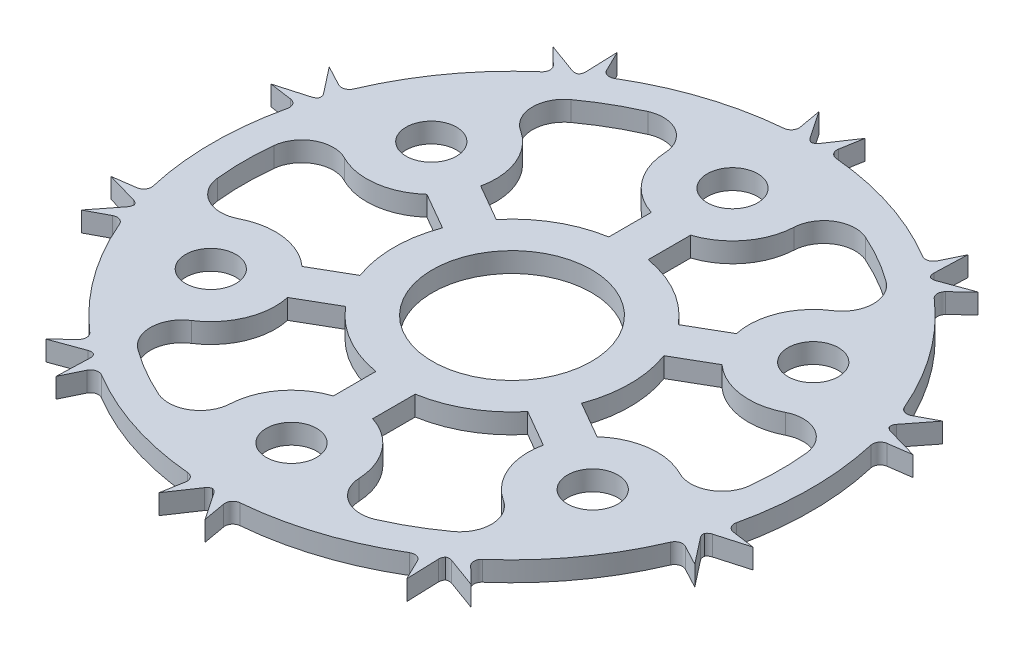
SolidWorks part; units mm, degrees
note: '?' marks a value the reader was unsure of.
material "Commercially Pure CP-Ti UNS R50700  Grade 4 (SS)"
ref_plane "Front Plane" through (0, 0, 0) normal (0, 0, 1) x (1, 0, 0)
ref_plane "Top Plane" through (0, 0, 0) normal (0, 1, 0) x (1, 0, 0)
ref_plane "Right Plane" through (0, 0, 0) normal (1, 0, 0) x (0, 0, -1)
other "Bounding Box"
ref_plane "Default Plane" through (13.8565, 3.175, 6.7999) normal (0, -1, 0) x (-1, 0, 0)
sketch "Sketch1" plane through (0, 0, 0) normal (0, 1, 0) x (1, 0, 0)
  line L0 (17.9605, -17.9605) -> (0, 0) construction
  line L1 (0, 0) -> (17.9605, 17.9605) construction
  line L2 (0, 0) -> (0, 25.4) construction
  circle A0 centre (0, 0) radius 25.4
  point P3 (0, 25.4)
  point P4 (25.4, 0)
  point P5 (-25.4, 0)
  point P6 (0, -25.4)
  point P7 (17.9605, 17.9605)
  point P8 (17.9605, -17.9605)
  dimension "D1" = 50.8
  dimension "D2" = 45
extrude "Boss-Extrude1" add sketch "Sketch1" along normal mid plane 15.24
ref_plane "Plane2" through (-25.4, 0, 0) normal (-1, 0, 0) x (0, 0, 1)
sketch "Sketch9" plane through (-25.4, 0, 0) normal (-1, 0, 0) x (0, 0, 1)
  line L0 (-0.635, -7.62) -> (0.635, -7.62)
  line L1 (-25.4, -7.62) -> (25.4, -7.62) construction
  line L2 (0.635, -7.62) -> (0.635, 0)
  line L3 (25.4, 7.62) -> (-25.4, 7.62) construction
  line L5 (-0.635, 0) -> (-0.635, -7.62)
  line L6 (0.635, -7.62) -> (0, -7.62) construction
  line L7 (0, -7.62) -> (0, 7.62) construction
  line L9 (-0.635, 0) -> (0.635, 0) construction
  line L10 (0.635, 0) -> (0.635, 7.62)
  line L11 (0.635, 7.62) -> (-0.635, 7.62)
  line L13 (-0.635, 7.62) -> (-0.635, 0)
  point P14 (0, 0)
  dimension "D2" = 1.27
extrude "Cut-Extrude4" cut sketch "Sketch9" against normal blind 0.635
sketch "Sketch4" plane through (0, 0, 0) normal (0, 0, 1) x (1, 0, 0)
  line L0 (-25.4, -7.62) -> (-22.225, -7.62)
  line L1 (-25.3921, -7.62) -> (25.4, -7.62) construction
  line L4 (25.4, 7.62) -> (-25.3921, 7.62) construction
  line L5 (-22.225, 7.62) -> (-25.4, 7.62)
  line L6 (-25.4, 7.62) -> (-25.4, -7.62)
  line L7 (-9.525, 0) -> (0, 0) construction
  line L8 (-22.225, -7.62) -> (-22.225, -5.08)
  line L9 (-22.225, -5.08) -> (-13.9469, -1.7687)
  line L10 (-13.9469, 1.7687) -> (-22.225, 5.08)
  line L11 (-22.225, 5.08) -> (-22.225, 7.62)
  arc A0 (-13.9469, 1.7687) -> (-13.9469, -1.7687) centre (-14.6544, 0) cw
  point P17 (-25.4, 0)
  dimension "D4" = 1.905
  dimension "D1" = 3.175
  dimension "D2" = 15.875
  dimension "D3" = 2.54
pattern_circular "CirPattern2" count 20 over 360 about axis through (0, 0, 0) along (0, 1, 0) of "Cut-Extrude4"
ref_axis "Axis1" through (0, -55, 0) along (0, 1, 0)
sketch "Sketch3" plane through (0, 7.62, 0) normal (0, 1, 0) x (1, 0, 0)
  line L0 (0, 0) -> (0, 17.78) construction
  line L1 (0, 17.78) -> (0, 25.4) construction
  circle A0 centre (0, 17.78) radius 1.397
  circle A1 centre (0, 0) radius 25.4 construction
  circle A2 centre (0, 17.78) radius 3.81
  dimension "D2" = 2.794
  dimension "D3" = 7.62
  dimension "D1" = 7.62
move or copy body "Body-Move/Copy1" [suppressed] parameters "D1"=0, "D2"=0, "D3"=0
revolve "Cut-Revolve2" cut sketch "Sketch4" angle 360 about axis through (0, -55, 0) along (0, 1, 0)
sketch "Sketch5" plane through (0, 7.62, 0) normal (0, 1, 0) x (1, 0, 0)
  circle A0 centre (0, 17.78) radius 3.81
  circle A1 centre (0, 17.78) radius 1.397 construction
  circle A3 centre (0, 17.78) radius 1.397
  circle A4 centre (0, 17.78) radius 3.81 construction
extrude "Boss-Extrude2" add sketch "Sketch5" against normal through all
sketch "Sketch12" plane through (0, 7.62, 0) normal (0, 1, 0) x (1, 0, 0)
  line L0 (-15.3979, 8.89) -> (0, 0) construction
  line L1 (-15.3979, -8.89) -> (-15.3979, 8.89) construction
  line L2 (-15.3979, 8.89) -> (0, 17.78) construction
  line L3 (-15.3979, -8.89) -> (0, 0) construction
  line L4 (0, 0) -> (0, 17.78) construction
  circle A0 centre (-15.3979, 8.89) radius 3.81
  circle A1 centre (0, 17.78) radius 3.81 construction
  dimension "D3" = 120
extrude "Boss-Extrude6" add sketch "Sketch12" against normal through all
sketch "Sketch17" plane through (0, 0, 0) normal (0, 1, 0) x (1, 0, 0)
  line L0 (0, 17.78) -> (0, 0) construction
  line L1 (0, 0) -> (-15.3979, 8.89) construction
  line L2 (0, 0) -> (-15.3979, -8.89) construction
  line L3 (-18.6975, -10.795) -> (-19.2474, -11.1125)
  line L4 (0, 21.59) -> (0, 22.225)
  line L5 (-17.3029, -5.5904) -> (-15.2513, -4.406)
  line L6 (-15.2513, 4.406) -> (-17.3029, 5.5904)
  line L7 (-13.4929, 12.1896) -> (-11.4413, 11.0051)
  line L8 (-3.81, 17.78) -> (-3.81, 15.411)
  circle A0 centre (0, 17.78) radius 3.81 construction
  circle A1 centre (-15.3979, 8.89) radius 3.81 construction
  arc A2 (0, 21.59) -> (-3.81, 17.78) centre (0, 17.78) ccw
  arc A3 (-13.4929, 12.1896) -> (-17.3029, 5.5904) centre (-15.3979, 8.89) ccw
  arc A5 (-3.81, 15.411) -> (-11.4413, 11.0051) centre (0, 0) ccw
  circle A6 centre (0, 17.78) radius 1.397 construction
  arc A7 (-17.3029, -5.5904) -> (-18.6975, -10.795) centre (-15.3979, -8.89) ccw
  circle A8 centre (0, 0) radius 22.225 construction
  circle A9 centre (0, 17.78) radius 1.397
  circle A10 centre (0, 0) radius 22.225 construction
  arc A11 (0, 22.225) -> (-19.2474, -11.1125) centre (0, 0) ccw
  arc A12 (-15.2513, 4.406) -> (-15.2513, -4.406) centre (0, 0) ccw
  circle A13 centre (-15.3979, 8.89) radius 1.397
  circle A15 centre (-15.3979, -8.89) radius 1.397
  dimension "D1" = 6.35
extrude "Cut-Extrude5" cut sketch "Sketch17" against normal through all both and the other way through all
pattern_circular "CirPattern1" count 3 over 360 about axis through (0, 0, 0) along (0, 1, 0) of "Boss-Extrude2", "Boss-Extrude6", "Cut-Extrude5"
sketch "Sketch24" plane through (0, -7.62, 0) normal (0, -1, 0) x (1, 0, 0)
  line L1 (5.4993, -9.525) -> (10.9985, 0)
  line L2 (10.9985, 0) -> (5.4993, 9.525)
  line L3 (5.4993, 9.525) -> (-5.4993, 9.525)
  line L4 (-5.4993, 9.525) -> (-10.9985, 0)
  line L5 (-10.9985, 0) -> (-5.4993, -9.525)
  line L6 (-5.4993, -9.525) -> (5.4993, -9.525)
  circle A0 centre (0, 0) radius 6.35 construction
  circle A1 centre (0, 0) radius 9.525 construction
  dimension "D1" = 12.7
  dimension "D2" = 19.05
extrude "Cut-Extrude7" cut sketch "Sketch24" against normal through all
sketch "Sketch33" [suppressed] plane through (0, -7.62, 0) normal (0, -1, 0) x (1, 0, 0)
  line L1 (-6.35, -6.35) -> (6.35, -6.35) construction
  line L2 (-6.35, -6.35) -> (-6.35, 6.35) construction
  line L3 (-6.35, 6.35) -> (6.35, 6.35) construction
  line L4 (6.35, -6.35) -> (6.35, 6.35) construction
  line L5 (-6.35, -6.35) -> (6.35, 6.35) construction
  line L6 (-6.35, 6.35) -> (6.35, -6.35) construction
  circle A0 centre (-6.35, 6.35) radius 2.4892
  circle A1 centre (6.35, 6.35) radius 2.4892
  circle A2 centre (6.35, -6.35) radius 2.4892
  circle A3 centre (-6.35, -6.35) radius 2.4892
  point P0 (0, 0)
  dimension "D1" = 4.9784
  dimension "D2" = 12.7
extrude "Cut-Extrude8" [suppressed] cut sketch "Sketch33" against normal through all
combine bodies "Combine3" [suppressed] bodies to combine 116 167
delete or keep bodies "Body-Delete/Keep 4" [suppressed] bodies 194
sketch "Sketch7" [suppressed] plane through (0, -8.255, 0) normal (0, -1, 0) x (1, 0, 0)
  circle A0 centre (0, 0) radius 44.45
  circle A1 centre (0, 0) radius 38.1 construction
  dimension "D1" = 6.35
extrude "Boss-Extrude4" [suppressed] add sketch "Sketch7" against normal offset from surface (19.685 mm away) 3.175 separate body
combine bodies "Combine2" [suppressed] operation type? add bodies to combine 110 114
sketch "Sketch15" [suppressed] plane through (0, 0, 0) normal (1, 0, 0) x (0, 0, -1)
  line L0 (-38.1, -8.255) -> (-43.18, -13.335)
  line L1 (-43.18, -13.335) -> (-36.83, -13.335)
  line L2 (-36.83, -13.335) -> (-31.75, -8.255)
  line L3 (-31.75, -8.255) -> (-38.1, -8.255)
  dimension "D1" = 5.08
  dimension "D2" = 45
  dimension "D3" = 6.35
ref_axis "Axis2" [suppressed] through (0, -9.0805, 0) along (0, 1, 0)?
revolve "Revolve1" [suppressed] add sketch "Sketch15" angle 360 about axis through (0, -9.0805, 0) along (0, 1, 0)
fillet "Fillet4" [suppressed] radius 6.35
sketch "Sketch27" [suppressed] plane through (0, 11.43, 0) normal (0, 1, 0) x (1, 0, 0)
  line L0 (37.5671, 6.35) -> (44.45, 6.35)
  line L1 (44.45, -6.35) -> (37.5671, -6.35)
  line L2 (38.1, 0) -> (44.45, 0) construction
  circle A0 centre (44.45, 0) radius 1.905
  arc A1 (37.5671, -6.35) -> (37.5671, 6.35) centre (0, 0) ccw
  circle A2 centre (0, 0) radius 38.1 construction
  arc A3 (44.45, 6.35) -> (44.45, -6.35) centre (44.45, 0) cw
  dimension "D2" = 3.81
  dimension "D3" = 6.35
  dimension "D1" = 6.35
extrude "Boss-Extrude13" [suppressed] add sketch "Sketch27" against normal blind 9.525
pattern_circular "CirPattern7" [suppressed] count 3 over 360
split "Split1" [suppressed] bodies to split 124
sketch "Sketch19" [suppressed] plane through (0, 11.43, 0) normal (0, 1, 0) x (1, 0, 0)
  line L0 (-20.447, 35.4152) -> (-19.177, 33.2155)
  line L1 (-20.447, -35.4152) -> (-19.177, -33.2155)
  line L2 (-40.894, 0) -> (0, 0) construction
  arc A0 (-19.177, 33.2155) -> (-19.177, -33.2155) centre (0, 0) ccw
  circle A1 centre (0, 0) radius 38.1 construction
  arc A2 (-20.447, 35.4152) -> (-20.447, -35.4152) centre (0, 0) ccw
  dimension "D2" = 2.54
  dimension "D3" = 0.254
  dimension "D1" = 120
extrude "Boss-Extrude10" [suppressed] add sketch "Sketch19" against normal blind 6.35 separate body
sketch "Sketch21" [suppressed] plane through (0, 11.43, 0) normal (0, 1, 0) x (1, 0, 0)
  line L0 (-19.177, 33.2155) -> (-19.05, 32.9956)
  line L1 (-19.177, -33.2155) -> (-19.05, -32.9956)
  line L2 (-19.177, 33.2155) -> (-20.447, 35.4152) construction
  line L3 (-20.447, -35.4152) -> (-19.177, -33.2155) construction
  arc A1 (-19.177, 33.2155) -> (-19.177, -33.2155) centre (0, 0) ccw construction
  arc A2 (-19.05, 32.9956) -> (-19.05, -32.9956) centre (0, 0) ccw
  arc A3 (-19.177, 33.2155) -> (-19.177, -33.2155) centre (0, 0) ccw
  circle A4 centre (0, 0) radius 38.1 construction
extrude "Boss-Extrude11" [suppressed] add sketch "Sketch21" against normal blind 3.1496
pattern_circular "CirPattern6" [suppressed] count 3 over 360
combine bodies "Combine4" [suppressed] bodies to combine 137 137 135 134
chamfer "Chamfer4" [suppressed] distance 0.635 angle 45
delete or keep bodies "Body-Delete/Keep 1" [suppressed] type delete bodies bodies 133
delete or keep bodies "Body-Delete/Keep 2" [suppressed] type delete bodies bodies 121
mirror "Mirror1" [suppressed] about plane through (0, 0, 0) normal (1, 0, 0)
delete or keep bodies "Body-Delete/Keep 3" [suppressed] type delete bodies bodies 121
sketch "Sketch28" [suppressed] plane through (0, 8.255, 0) normal (0, -1, 0) x (1, 0, 0)
  circle A0 centre (0, 0) radius 15.24
  dimension "D1" = 30.48
extrude "Boss-Extrude14" [suppressed] add sketch "Sketch28" along normal blind 0.635
sketch "Sketch29" [suppressed] plane through (0, 7.62, 0) normal (0, -1, 0) x (1, 0, 0)
  circle A0 centre (0, 0) radius 9.144
  dimension "D1" = 18.288
extrude "Boss-Extrude15" [suppressed] add sketch "Sketch29" along normal blind 10.16
sketch "Sketch30" plane through (0, -7.62, 0) normal (0, -1, 0) x (1, 0, 0)
  circle A12 centre (0, 0) radius 24.13
  circle A13 centre (0, 0) radius 21.59
  circle A14 centre (0, 0) radius 25.4 construction
  dimension "D1" = 1.27
  dimension "D2" = 2.54
extrude "Boss-Extrude16" add sketch "Sketch30" along normal blind 1.6002 separate body
sketch "Sketch31" plane through (0, -9.2202, 0) normal (0, -1, 0) x (1, 0, 0)
  line L0 (-5.207, 17.78) -> (-5.207, 23.5615)
  line L1 (-5.207, 23.5615) -> (5.207, 23.5615)
  line L2 (5.207, 23.5615) -> (5.207, 17.78)
  line L3 (0, 0) -> (0, 17.78) construction
  line L4 (-1.5875, 12.8209) -> (1.5875, 12.8209) construction
  line L5 (-1.5875, 12.8209) -> (-1.5875, 7.62)
  line L6 (-1.5875, 7.62) -> (1.5875, 7.62)
  line L7 (1.5875, 12.8209) -> (1.5875, 7.62)
  line L8 (-1.5875, 12.8209) -> (1.5875, 7.62) construction
  line L9 (-1.5875, 7.62) -> (1.5875, 12.8209) construction
  arc A0 (-1.5875, 12.8209) -> (-5.207, 17.78) centre (0, 17.78) cw
  circle A1 centre (0, 17.78) radius 2.032
  arc A2 (5.207, 17.78) -> (1.5875, 12.8209) centre (0, 17.78) cw
  circle A3 centre (0, 17.78) radius 1.397 construction
  circle A4 centre (0, 0) radius 24.13 construction
  point P0 (0, 10.2204)
  dimension "D1" = 3.175
  dimension "D2" = 4.064
  dimension "D3" = 7.62
  dimension "D4" = 3.175
extrude "Boss-Extrude17" add sketch "Sketch31" against normal up to surface (1.6002 mm away) up to face at (0, -7.62, -24.13)
fillet "Fillet6" radius 2.54 2 edges at (5.207, -8.4201, 20.9527) (-5.207, -8.4201, 20.9527)
pattern_circular "CirPattern8" count 6 over 360 about axis through (0, 0, 0) along (0, 1, 0) of "Boss-Extrude17", "Fillet6"
sketch "Sketch32" plane through (0, -9.2202, 0) normal (0, -1, 0) x (1, 0, 0)
  line L0 (0, 0) -> (-1.8604, 26.605) construction
  line L1 (1.8604, 26.605) -> (0.1905, 24.1292)
  line L2 (0, 0) -> (0, 26.67) construction
  line L3 (-1.4167, 24.0884) -> (-1.8604, 26.605)
  line L4 (-1.8604, 26.605) -> (-0.1905, 24.1292)
  line L5 (-0.1905, 24.1292) -> (-1.4167, 24.0884)
  line L6 (1.4167, 24.0884) -> (1.8604, 26.605)
  line L7 (0.1905, 24.1292) -> (1.4167, 24.0884)
  circle A0 centre (0, 0) radius 24.13 construction
  circle A1 centre (0, 0) radius 26.67 construction
  circle A2 centre (0, 0) radius 25.4 construction
  dimension "D2" = 1.27
  dimension "D1" = 6
  dimension "D3" = 30
  dimension "D4" = 4
extrude "Boss-Extrude18" add sketch "Sketch32" against normal up to surface (1.6002 mm away) up to face at (0, -7.62, -24.13)
fillet "Fillet7" radius 0.635 4 edges at (1.4167, -8.4201, 24.0884) (0.1905, -8.4201, 24.1292) (-0.1905, -8.4201, 24.1292) (-1.4167, -8.4201, 24.0884)
pattern_circular "CirPattern9" count 10 over 360 about axis through (0, 0, 0) along (0, 1, 0) of "Boss-Extrude18", "Fillet7"
sketch "Sketch34" plane through (0, -9.2202, 0) normal (0, -1, 0) x (1, 0, 0)
  circle A0 centre (0, 0) radius 6.4135
  circle A1 centre (0, 0) radius 9.525
  dimension "D1" = 12.827
  dimension "D2" = 19.05
extrude "Boss-Extrude19" add sketch "Sketch34" against normal up to surface (1.6002 mm away) up to face at (0, -7.62, 0)
delete or keep bodies "Body-Delete/Keep 5" bodies 197
